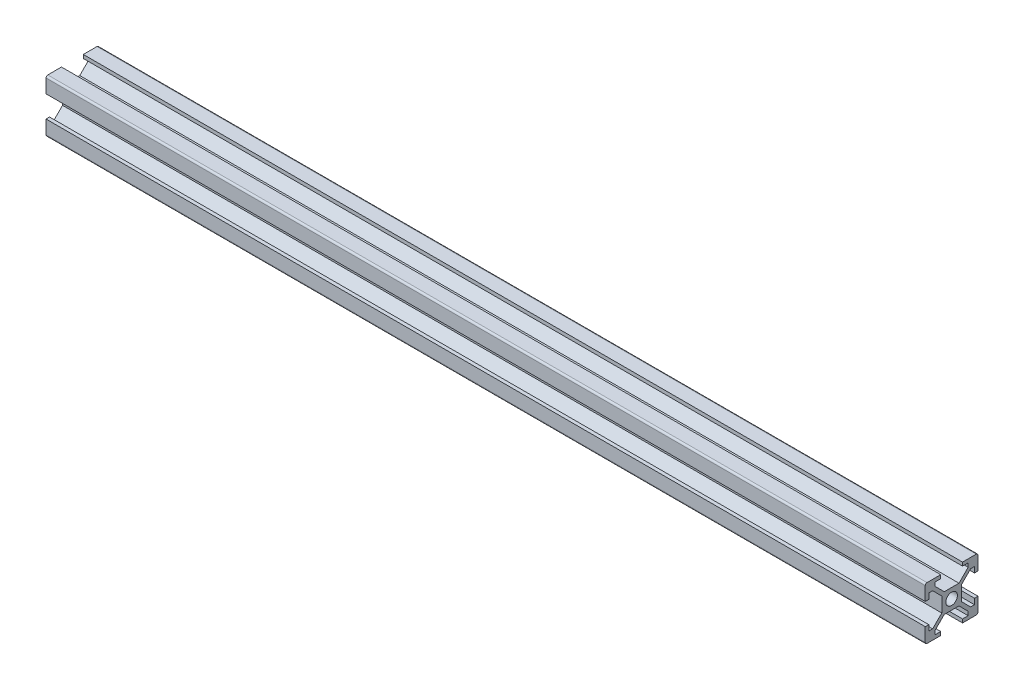
SolidWorks part; units mm, degrees
ref_plane "前视基准面" through (0, 0, 0) normal (0, 0, 1) x (1, 0, 0)
ref_plane "上视基准面" through (0, 0, 0) normal (0, 1, 0) x (1, 0, 0)
ref_plane "右视基准面" through (0, 0, 0) normal (1, 0, 0) x (0, 0, -1)
sketch "草图2" plane through (0, 0, 0) normal (1, 0, 0) x (0, 0, -1)
  line L0 (-3.1, 7.5) -> (3.1, 7.5)
  line L1 (-7, 7.5) -> (7, 7.5)
  line L2 (-7.5, 7) -> (-7.5, -7)
  line L3 (-7, -7.5) -> (7, -7.5)
  line L4 (7.5, 7) -> (7.5, -7)
  line L5 (-3.1, 7.5) -> (-3.1, 6.5)
  line L6 (-3.1, 6.5) -> (-4.7, 6.5)
  line L7 (-4.7, 6.5) -> (-4.7, 5.4071)
  line L8 (-4.7, 5.4071) -> (-2.0929, 2.8)
  line L9 (-2.0929, 2.8) -> (2.0929, 2.8)
  line L10 (2.0929, 2.8) -> (4.7, 5.4071)
  line L11 (4.7, 5.4071) -> (4.7, 6.5)
  line L12 (4.7, 6.5) -> (3.1, 6.5)
  line L13 (3.1, 6.5) -> (3.1, 7.5)
  line L14 (-7.5, -7.5) -> (7.5, 7.5) construction
  line L15 (7.5, -7.5) -> (-7.5, 7.5) construction
  line L17 (-2.8, 2.8) -> (2.8, 2.8)
  line L18 (-2.8, 2.8) -> (-2.8, -2.8)
  line L19 (-2.8, -2.8) -> (2.8, -2.8)
  line L20 (2.8, 2.8) -> (2.8, -2.8)
  line L21 (-2.8, 2.8) -> (2.8, -2.8) construction
  line L22 (-2.8, -2.8) -> (2.8, 2.8) construction
  line L52 (7.5, 3.1) -> (7.5, -3.1)
  line L53 (6.5, -3.1) -> (7.5, -3.1)
  line L54 (6.5, -4.7) -> (6.5, -3.1)
  line L55 (5.4071, -4.7) -> (6.5, -4.7)
  line L56 (2.8, -2.0929) -> (5.4071, -4.7)
  line L57 (2.8, 2.0929) -> (2.8, -2.0929)
  line L58 (5.4071, 4.7) -> (2.8, 2.0929)
  line L59 (6.5, 4.7) -> (5.4071, 4.7)
  line L60 (6.5, 3.1) -> (6.5, 4.7)
  line L61 (7.5, 3.1) -> (6.5, 3.1)
  line L62 (3.1, -7.5) -> (-3.1, -7.5)
  line L63 (-3.1, -6.5) -> (-3.1, -7.5)
  line L64 (-4.7, -6.5) -> (-3.1, -6.5)
  line L65 (-4.7, -5.4071) -> (-4.7, -6.5)
  line L66 (-2.0929, -2.8) -> (-4.7, -5.4071)
  line L67 (2.0929, -2.8) -> (-2.0929, -2.8)
  line L68 (4.7, -5.4071) -> (2.0929, -2.8)
  line L69 (4.7, -6.5) -> (4.7, -5.4071)
  line L70 (3.1, -6.5) -> (4.7, -6.5)
  line L71 (3.1, -7.5) -> (3.1, -6.5)
  line L72 (-7.5, -3.1) -> (-7.5, 3.1)
  line L73 (-6.5, 3.1) -> (-7.5, 3.1)
  line L74 (-6.5, 4.7) -> (-6.5, 3.1)
  line L75 (-5.4071, 4.7) -> (-6.5, 4.7)
  line L76 (-2.8, 2.0929) -> (-5.4071, 4.7)
  line L77 (-2.8, -2.0929) -> (-2.8, 2.0929)
  line L78 (-5.4071, -4.7) -> (-2.8, -2.0929)
  line L79 (-6.5, -4.7) -> (-5.4071, -4.7)
  line L80 (-6.5, -3.1) -> (-6.5, -4.7)
  line L81 (-7.5, -3.1) -> (-6.5, -3.1)
  line L82 (0, 0) -> (2.0929, 2.8) construction
  line L83 (0, 0) -> (2.8, -2.0929) construction
  circle A0 centre (0, 0) radius 1.65
  circle A1 centre (-7, 7) radius 0.5 construction
  circle A2 centre (-7, -7) radius 0.5 construction
  circle A3 centre (7, -7) radius 0.5 construction
  circle A4 centre (7, 7) radius 0.5 construction
  arc A5 (7, 7.5) -> (7.5, 7) centre (7, 7) cw
  arc A6 (7, -7.5) -> (7.5, -7) centre (7, -7) ccw
  arc A7 (-7.5, -7) -> (-7, -7.5) centre (-7, -7) ccw
  arc A8 (-7, 7.5) -> (-7.5, 7) centre (-7, 7) ccw
  point P16 (0, 0)
  point P50 (0, 7.5)
  point P52 (7.5, 0)
  dimension "D3" = 3.3
  dimension "D12" = 1
  dimension "D13" = 1
  dimension "D14" = 1
  dimension "D15" = 1
  dimension "D16" = 0.5
  dimension "D1" = 15
  dimension "D2" = 6.2
  dimension "D4" = 5.6
  dimension "D5" = 9.4
  dimension "D6" = 0.5
  dimension "D7" = 0.5
  dimension "D8" = 4.7
  dimension "D9" = 1
  dimension "D10" = 4
  dimension "D11" = 90
extrude "凸台-拉伸1" add sketch "草图2" along normal blind 250 contours L2 A7 L3 A6 L4 A5 L1 A8
extrude "切除-拉伸2" cut sketch "草图2<4>" against normal through all and the other way through all contours L3 L71 L70 L69 L68 L19 L66 L65 L64 L63 | L2 L81 L80 L79 L78 L18 L76 L75 L74 L73 | L12 L13 L0 L5 L6 L7 L8 L9 L10 L11 | L4 L61 L60 L59 L58 L20 L56 L55 L54 L53 | A0 region at (0, 5.2713, 0) region at (0, 0, 5.2713) region at (0, 0, -5.2713) region at (0, -5.2713, 0) region at (0, 0, 0)
sketch "草图2<4>" plane through (0, 0, 0) normal (1, 0, 0) x (0, 0, -1) same geometry as "草图2"
